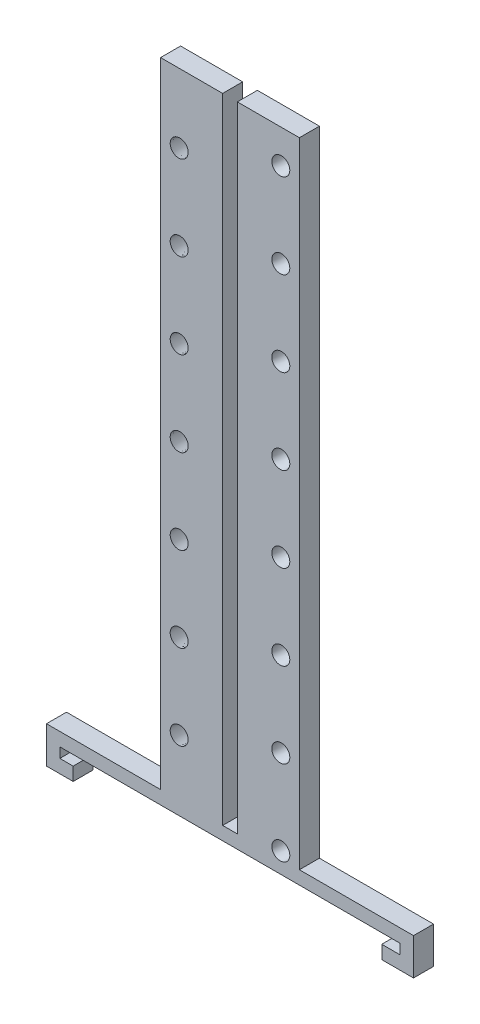
SolidWorks part; units mm, degrees
ref_plane "Alzado" through (0, 0, 0) normal (0, 0, 1) x (1, 0, 0)
ref_plane "Planta" through (0, 0, 0) normal (0, 1, 0) x (1, 0, 0)
ref_plane "Vista lateral" through (0, 0, 0) normal (1, 0, 0) x (0, 0, -1)
sketch "Croquis1" plane through (0, 0, 0) normal (0, 0, 1) x (1, 0, 0)
  line L0 (-72.8615, -40.7677) -> (-68.8615, -40.7677)
  line L1 (-55.7615, 59.7323) -> (-46.4615, 59.7323)
  line L2 (-46.4615, 59.7323) -> (-46.4615, -35.2677)
  line L3 (-55.7615, -35.2677) -> (-72.8615, -35.2677)
  line L5 (-68.8615, -40.7677) -> (-68.8615, -38.7677)
  line L6 (-68.8615, -38.7677) -> (-70.8615, -38.7677)
  line L7 (-70.8615, -38.7677) -> (-70.8615, -37.2677)
  line L8 (-70.8615, -37.2677) -> (-19.8615, -37.2677)
  line L9 (-19.8615, -37.2677) -> (-19.8615, -38.7677)
  line L10 (-19.8615, -38.7677) -> (-22.6185, -38.7677)
  line L11 (-22.6185, -38.7677) -> (-22.6185, -40.7677)
  line L12 (-22.6185, -40.7677) -> (-17.8615, -40.7677)
  line L13 (-34.9615, -35.2677) -> (-17.8615, -35.2677)
  line L14 (-17.8615, -35.2677) -> (-17.8615, -40.7677)
  line L15 (-34.9615, -35.2677) -> (-34.9615, 59.7323)
  line L16 (-44.2615, 59.7323) -> (-34.9615, 59.7323)
  line L17 (-55.7615, 59.7323) -> (-55.7615, -35.2677)
  line L18 (-72.8615, -35.2677) -> (-72.8615, -40.7677)
  line L19 (-44.2615, -35.2677) -> (-44.2615, 59.7323)
  line L20 (-46.4615, -35.2677) -> (-44.2615, -35.2677)
  dimension "D1" = 95
  dimension "D2" = 55
  dimension "D3" = 1.5
  dimension "D4" = 2
  dimension "D5" = 5.5
  dimension "D6" = 2
  dimension "D7" = 2
  dimension "D8" = 2
  dimension "D9" = 5.5
  dimension "D10" = 2
  dimension "D11" = 1.5
  dimension "D12" = 95
extrude "Saliente-Extruir1" add sketch "Croquis1" along normal blind 3
sketch "Croquis2" plane through (0, -35.2677, 0) normal (0, 1, 0) x (1, 0, 0)
  circle A0 centre (-45.3615, -1) radius 7.88
curve "Hélice/Espiral1" pitch 12.7 height 101.6 radius 7.88 centre (-45.3615, -35.2677, 1) axis (0, 1, 0) start towards (0.7071, 0, 0.7071)
ref_plane "Plano1" through (-39.7895, 66.3323, 6.572) normal (0.6849, 0.2485, -0.6849) x (0.6439, 0.2336, 0.7286)
sketch "Croquis4" plane through (-39.7895, 66.3323, 6.572) normal (0.6849, 0.2485, -0.6849) x (0.6439, 0.2336, 0.7286)
  circle A0 centre (0.0006, 0.0013) radius 1.3
sweep "Cortar-Barrer1" cut profiles "Croquis4" path "Hélice/Espiral1"
